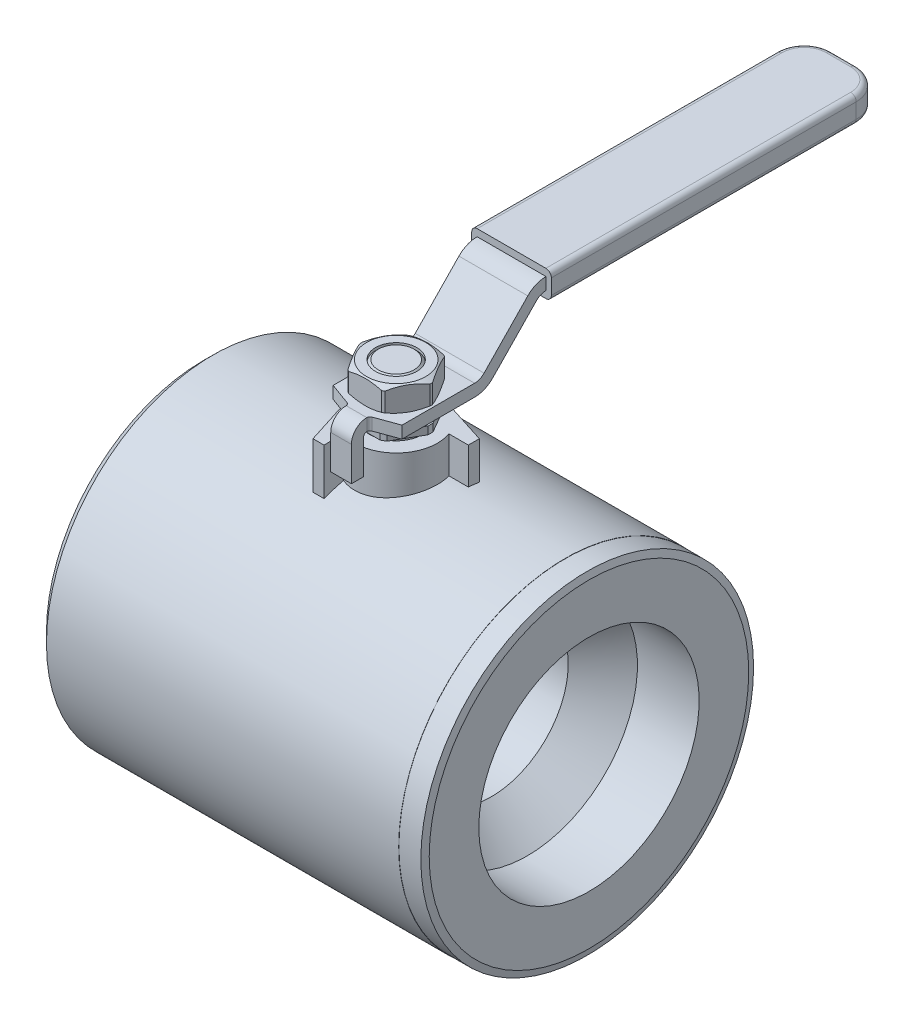
SolidWorks part; units mm, degrees
ref_plane "Plane1" through (0, 0, 0) normal (0, 0, 1) x (1, 0, 0)
ref_plane "Plane2" through (0, 0, 0) normal (0, 1, 0) x (1, 0, 0)
ref_plane "Plane3" through (0, 0, 0) normal (1, 0, 0) x (0, 0, -1)
sketch "Sketch1" plane through (0, 0, 0) normal (0, 0, 1) x (1, 0, 0)
  line L1 (-30.226, 1.8525) -> (-21.9379, -5.8069)
  line L2 (-31.496, 1.8525) -> (-44.45, 1.8525)
  line L3 (-21.9379, -5.8069) -> (21.9379, -5.8069)
  line L4 (31.496, 1.8525) -> (30.226, 1.8525)
  line L5 (31.496, 1.8525) -> (44.45, 1.8525)
  line L6 (44.45, 1.8525) -> (44.45, 13.2825)
  line L7 (44.45, 13.2825) -> (44.0416, 14.8065)
  line L8 (44.0416, 14.8065) -> (38.989, 14.8065)
  line L9 (38.989, 14.8065) -> (38.989, 14.859)
  line L10 (38.989, 14.859) -> (-42.2148, 14.859)
  line L11 (-42.2148, 14.859) -> (-44.45, 12.6238)
  line L12 (-44.45, 12.6238) -> (-44.45, 1.8525)
  line L13 (0, 0) -> (0, 50.9028) construction
  line L14 (30.226, 1.8525) -> (21.9379, -5.8069)
  line L15 (-31.496, 1.8525) -> (-30.226, 1.8525)
  line L16 (44.45, 1.8525) -> (44.45, -23.5475) construction
  line L17 (-26.3766, -23.5475) -> (44.45, -23.5475) construction
  dimension "D1" = 14.224
  dimension "D2" = 25.4
  dimension "D3" = 11.43
  dimension "D6" = 1.27
  dimension "D7" = 45
  dimension "D8" = 2.2352
  dimension "D9" = 15
  dimension "D10" = 1.524
  dimension "D14" = 88.9
  dimension "D15" = 5.461
revolve "Revolve1" add sketch "Sketch1" angle 360 about L17
sketch "Sketch6" plane through (0, 0, 0) normal (0, 0, 1) x (1, 0, 0)
  line L0 (0, 12.7) -> (0, -23.0983) construction
  line L1 (0, 12.7) -> (6.096, 12.7)
  line L2 (6.096, 12.7) -> (6.096, 24.257)
  line L3 (6.096, 24.257) -> (7.9375, 24.257)
  line L4 (7.9375, 24.257) -> (7.9375, 26.035)
  line L5 (7.9375, 26.035) -> (4.7625, 26.035)
  line L6 (4.7625, 26.035) -> (4.7625, 29.21)
  line L7 (4.7625, 29.21) -> (6.8199, 29.21)
  line L8 (6.8199, 29.21) -> (8.0899, 29.9432)
  line L9 (8.0899, 29.9432) -> (8.0899, 34.3188)
  line L10 (8.0899, 34.3188) -> (6.8199, 35.052)
  line L11 (6.8199, 35.052) -> (4.7625, 35.052)
  line L12 (4.7625, 35.052) -> (4.7625, 34.417)
  line L13 (4.7625, 34.417) -> (4.1275, 35.052)
  line L14 (4.1275, 35.052) -> (0, 35.052)
  line L15 (0, 35.052) -> (0, 12.7)
  dimension "D1" = 12.192
  dimension "D2" = 15.875
  dimension "D3" = 9.525
  dimension "D4" = 16.1798
  dimension "D5" = 45
  dimension "D6" = 0.635
  dimension "D7" = 30
  dimension "D8" = 30
  dimension "D9" = 1.27
  dimension "D10" = 35.052
  dimension "D11" = 1.778
  dimension "D12" = 5.842
  dimension "D13" = 3.175
  dimension "D14" = 12.7
revolve "Revolve2" add sketch "Sketch6" angle 360 about L0
sketch "Sketch7" plane through (0, 35.052, 0) normal (0, 1, 0) x (-1, 0, 0)
  line L1 (4.1244, 7.1438) -> (-4.1244, 7.1437)
  line L2 (-4.1244, 7.1437) -> (-8.2489, 0)
  line L3 (-8.2489, 0) -> (-4.1244, -7.1437)
  line L4 (-4.1244, -7.1437) -> (4.1244, -7.1437)
  line L5 (4.1244, -7.1437) -> (8.2489, 0)
  line L6 (8.2489, 0) -> (4.1244, 7.1438)
  circle A0 centre (0, 0) radius 18.4551
  circle A1 centre (0, 0) radius 7.1438 construction
  dimension "D1" = 14.2875
extrude "Cut-Extrude4" cut sketch "Sketch7" against normal blind 15.24
sketch "Sketch8" plane through (0, 0, 0) normal (1, 0, 0) x (0, 0, -1)
  line L0 (-9.906, 17.78) -> (-9.906, 25.654)
  line L1 (-9.144, 26.416) -> (10.141, 26.416)
  line L2 (14.3325, 28.1886) -> (24.4137, 38.5722)
  line L3 (26.6006, 39.497) -> (101.6, 39.497)
  line L4 (-9.906, 17.78) -> (-12.7, 17.78)
  line L5 (-12.7, 17.78) -> (-12.7, 25.654)
  line L6 (-9.144, 29.21) -> (10.141, 29.21)
  line L7 (12.3279, 30.1348) -> (22.4091, 40.5184)
  line L8 (26.6006, 42.291) -> (101.6, 42.291)
  line L9 (101.6, 42.291) -> (101.6, 39.497)
  line L10 (17.3685, 35.3266) -> (19.3731, 33.3804) construction
  line L11 (0.4985, 29.21) -> (0.4985, 26.416) construction
  line L12 (-6.8199, 29.21) -> (6.8199, 29.21) construction
  arc A0 (-9.144, 26.416) -> (-9.906, 25.654) centre (-9.144, 25.654) ccw
  arc A1 (-9.144, 29.21) -> (-12.7, 25.654) centre (-9.144, 25.654) ccw
  arc A2 (12.3279, 30.1348) -> (10.141, 29.21) centre (10.141, 32.258) cw
  arc A3 (26.6006, 39.497) -> (24.4137, 38.5722) centre (26.6006, 36.449) ccw
  arc A4 (14.3325, 28.1886) -> (10.141, 26.416) centre (10.141, 32.258) cw
  arc A5 (26.6006, 42.291) -> (22.4091, 40.5184) centre (26.6006, 36.449) ccw
  point P23 (11.43, 29.21)
  point P30 (24.13, 42.291)
  dimension "D8" = 0.762
  dimension "D9" = 3.556
  dimension "D10" = 3.048
  dimension "D11" = 5.842
  dimension "D1" = 2.794
  dimension "D2" = 11.43
  dimension "D3" = 12.7
  dimension "D4" = 114.3
  dimension "D5" = 15.875
  dimension "D6" = 12.7
  dimension "D7" = 11.43
extrude "Extrude2" add sketch "Sketch8" along normal mid plane 15.875
fillet "Fillet4" radius 4.7625 2 edges at (7.9375, 40.894, -101.6) (-7.9375, 40.894, -101.6)
sketch "Sketch9" plane through (0, 0, 0) normal (1, 0, 0) x (0, 0, -1)
  line L0 (26.6006, 43.9166) -> (26.6006, 37.8714)
  line L1 (26.6006, 37.8714) -> (103.2256, 37.8714)
  line L2 (103.2256, 37.8714) -> (103.2256, 43.9166)
  line L3 (103.2256, 43.9166) -> (26.6006, 43.9166)
  line L4 (101.6, 40.894) -> (26.6006, 40.894) construction
  line L5 (101.6, 42.291) -> (101.6, 39.497) construction
  line L6 (96.8375, 42.291) -> (26.6006, 42.291) construction
  dimension "D1" = 6.0452
  dimension "D2" = 1.6256
  dimension "D3" = 1.6256
extrude "Extrude3" add sketch "Sketch9" along normal mid plane 18.3642
fillet "Fillet5" radius 6.35 2 edges at (-9.1821, 40.894, -103.2256) (9.1821, 40.894, -103.2256)
fillet "Fillet6" radius 1.27 10 edges at (-9.1821, 37.8714, -61.7381) (-7.3222, 37.8714, -101.3657) (0, 37.8714, -103.2256) (7.3222, 37.8714, -101.3657) (9.1821, 37.8714, -61.7381) (-9.1821, 43.9166, -61.7381) (-7.3222, 43.9166, -101.3657) (0, 43.9166, -103.2256) (7.3222, 43.9166, -101.3657) (9.1821, 43.9166, -61.7381)
sketch "Sketch10" plane through (0, 29.21, 0) normal (0, 1, 0) x (-1, 0, 0)
  line L0 (-7.9375, 12.7) -> (-2.3813, 12.7)
  line L1 (-7.9375, 12.7) -> (7.9375, 12.7) construction
  line L2 (-2.3813, 12.7) -> (-2.3812, 9.144)
  line L3 (-2.8826, 8.428) -> (-7.9375, 6.5881)
  line L4 (-7.9375, 6.5881) -> (-7.9375, 12.7)
  line L5 (0, 12.7) -> (0, 19.6661) construction
  line L6 (7.9375, 6.5881) -> (7.9375, 12.7)
  line L7 (2.8826, 8.428) -> (7.9375, 6.5881)
  line L8 (2.3813, 12.7) -> (2.3812, 9.144)
  line L9 (7.9375, 12.7) -> (2.3813, 12.7)
  line L11 (-7.9375, 9.144) -> (7.9375, 9.144) construction
  arc A0 (-2.8826, 8.428) -> (-2.3812, 9.144) centre (-3.1432, 9.144) ccw
  arc A1 (2.8826, 8.428) -> (2.3812, 9.144) centre (3.1432, 9.144) cw
  point P15 (-2.3812, 8.6104)
  point P18 (2.3812, 8.6104)
  dimension "D2" = 0.762
  dimension "D1" = 4.7625
  dimension "D3" = 70
extrude "Cut-Extrude5" cut sketch "Sketch10" against normal blind 12.7
sketch "Sketch4" plane through (0, 0, 0) normal (0, 1, 0) x (1, 0, 0)
  line L0 (-3.175, -8.9803) -> (-3.175, -13.462)
  line L1 (8.9803, 3.175) -> (13.462, 3.175)
  line L2 (2.8858, 9.0773) -> (13.462, 5.715)
  line L3 (13.462, 5.715) -> (13.462, 3.175)
  line L4 (-9.0773, -2.8858) -> (-5.715, -13.462)
  line L5 (-5.715, -13.462) -> (-3.175, -13.462)
  arc A0 (-3.175, -8.9803) -> (8.9803, 3.175) centre (0, 0) ccw
  arc A1 (2.8858, 9.0773) -> (-9.0773, -2.8858) centre (0, 0) ccw
  dimension "D1" = 19.05
  dimension "D2" = 3.175
  dimension "D3" = 3.175
  dimension "D4" = 2.54
  dimension "D5" = 13.462
extrude "Extrude1" add sketch "Sketch4" along normal blind 20.574 from offset 2.54
other "CPoint1" parameters "Diameter"=50.8, "StubLength"=0
ref_axis "Axis1" through (54.45, -23.5475, 0) along (-1, 0, 0)
other "CPoint2" parameters "Diameter"=50.8, "StubLength"=0
ref_axis "Axis2" through (-54.45, -23.5475, 0) along (1, 0, 0)
sketch3d "3DSketch1"
  line L0 (44.45, -23.5475, 0) -> (-44.45, -23.5475, 0)
  point P5 (0, -23.5475, 0)
other "RPoint1"
